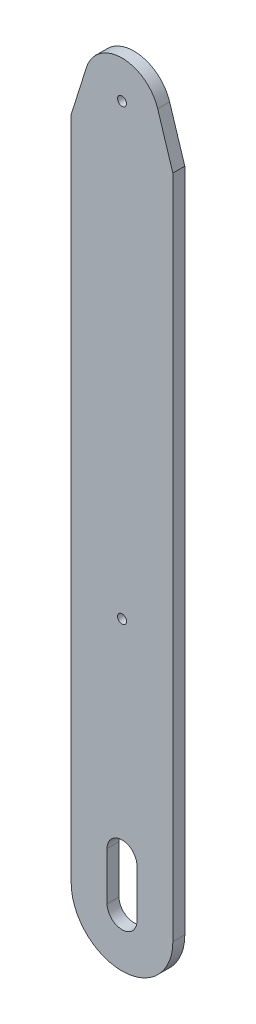
SolidWorks part; units mm, degrees
material "ABS PC"
ref_plane "Front" through (0, 0, 0) normal (0, 0, 1) x (1, 0, 0)
ref_plane "Top" through (0, 0, 0) normal (0, 1, 0) x (1, 0, 0)
ref_plane "Right" through (0, 0, 0) normal (1, 0, 0) x (0, 0, -1)
sketch "Esquisse1" plane through (0, 0, 0) normal (0, 0, 1) x (1, 0, 0)
  line L0 (0, -235) -> (0, -219) construction
  line L2 (-17, -12.3482) -> (-17, -235)
  line L4 (17, -12.3482) -> (17, -235)
  line L5 (-5, -235) -> (-5, -219)
  line L6 (5, -235) -> (5, -219)
  line L7 (-11.9215, 3.7588) -> (-17, -12.3482)
  line L8 (0, -50) -> (0, 50) construction
  line L9 (11.9215, 3.7588) -> (17, -12.3482)
  circle A0 centre (0, 0) radius 1.5
  arc A1 (-17, -235) -> (17, -235) centre (0, -235) ccw
  arc A2 (-5, -235) -> (5, -235) centre (0, -235) ccw
  arc A3 (5, -219) -> (-5, -219) centre (0, -219) ccw
  arc A4 (11.9215, 3.7588) -> (-11.9215, 3.7588) centre (0, 0) ccw
  circle A5 centre (0, -150) radius 1.5
  point P8 (0, -227)
  point P16 (0, 0)
  dimension "D1" = 10
  dimension "D3" = 35
  dimension "D4" = 235
  dimension "D5" = 3
  dimension "D6" = 16
  dimension "D7" = 38
  dimension "D8" = 25
  dimension "D9" = 264.5
  dimension "D10" = 150
  dimension "D2" = 34
base flange "Tôle de base pliée1" sketch "Esquisse1" thickness 4 reverse thickness direction no parameters "D1"=1
sketch "Lignes de pliage1" [suppressed] plane through (0, 0, 0) normal (0, 1, 0) x (1, 0, 0)
sketch "Cube de visualisation1" [suppressed] plane through (0, 0, 0) normal (0, 1, 0) x (1, 0, 0)
sheet metal parameters "Tôlerie1" thickness 4 parameters "D1"=1
flat pattern "Etat déplié1" [suppressed]
sketch "Lignes de pliage2" plane through (0, 0, 0) normal (0, 1, 0) x (1, 0, 0)
sketch3d "Cube de visualisation2" [suppressed]
  line L0 (17, 247.5, 0) -> (17, -17, 0) construction
  line L1 (-17, 247.5, 0) -> (-17, -17, 0) construction
  line L2 (17, 247.5, 0) -> (-17, 247.5, 0) construction
  line L3 (17, -17, 0) -> (-17, -17, 0) construction
